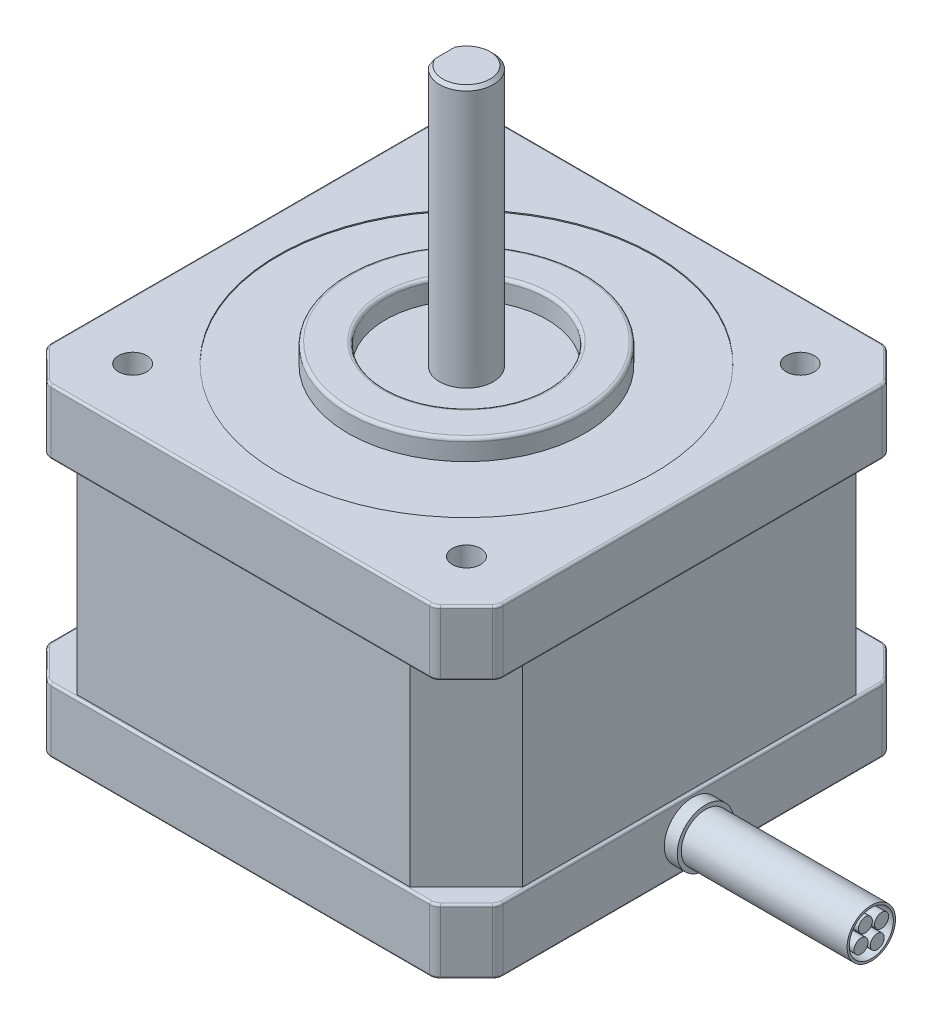
SolidWorks part; units mm, degrees
ref_plane "前视基准面" through (0, 0, 0) normal (0, 0, 1) x (1, 0, 0)
ref_plane "上视基准面" through (0, 0, 0) normal (0, 1, 0) x (1, 0, 0)
ref_plane "右视基准面" through (0, 0, 0) normal (1, 0, 0) x (0, 0, -1)
sketch "草图13" plane through (0, 0, 0) normal (0, 0, 1) x (1, 0, 0)
  line L0 (0, 0) -> (0, 30) construction
  dimension "L" = 30
sketch "草图1" plane through (0, 0, 0) normal (0, 1, 0) x (1, 0, 0)
  line L0 (0, 21) -> (0, -21) construction
  line L1 (-21, 21) -> (21, 21)
  line L2 (-21, 21) -> (-21, -21)
  line L3 (-21, -21) -> (21, -21)
  line L4 (21, 21) -> (21, -21)
  line L5 (-21, 0) -> (21, 0) construction
  dimension "D2" = 21
  dimension "W2" = 42
  dimension "D4" = 21
extrude "凸台-拉伸1" add sketch "草图1" along normal blind 30
chamfer "倒角3" distance 3 angle 45 4 edges at (21, 15, -21) (21, 15, 21) (-21, 15, 21) (-21, 15, -21)
sketch "草图2" plane through (0, 30, 0) normal (0, 1, 0) x (1, 0, 0)
  circle A0 centre (0, 0) radius 11
  dimension "E6" = 22
extrude "凸台-拉伸2" add sketch "草图2" along normal blind 1.8
ref_plane "基准面1" through (0, 6, 0) normal (0, -1, 0) x (1, 0, 0)
sketch "草图3" plane through (0, 30, 0) normal (0, 1, 0) x (1, 0, 0)
  line L0 (-2, 1.5) -> (-2, -1.5) construction
  circle A0 centre (0, 0) radius 2.5
  point P3 (2.5, 0)
  dimension "D1" = 4.5
  dimension "E4" = 5
extrude "凸台-拉伸3" add sketch "草图3" along normal blind 24
sketch "草图4" plane through (0, 6, 0) normal (0, -1, 0) x (1, 0, 0)
  line L0 (15.4716, 20.7) -> (-15.4716, 20.7)
  line L1 (-15.4716, 20.7) -> (-20.7, 15.4716)
  line L2 (-20.7, 15.4716) -> (-20.7, -15.4716)
  line L3 (-20.7, -15.4716) -> (-15.4716, -20.7)
  line L4 (-15.4716, -20.7) -> (15.4716, -20.7)
  line L5 (15.4716, -20.7) -> (20.7, -15.4716)
  line L6 (20.7, -15.4716) -> (20.7, 15.4716)
  line L7 (20.7, 15.4716) -> (15.4716, 20.7)
  line L8 (18, -21) -> (-18, -21) construction
  line L9 (-21, -18) -> (-21, 18) construction
  line L10 (21, 18) -> (21, -18) construction
  line L11 (-18, 21) -> (18, 21) construction
  line L15 (-18, 21) -> (-21, 18) construction
  line L21 (0, -21) -> (0, 21) construction
  line L22 (0, -21) -> (0, 21) construction
  line L23 (-21, 0) -> (21, 0) construction
  dimension "D1" = 0.3
  dimension "D2" = 0.3
  dimension "D3" = 0.3
  dimension "D4" = 0.3
  dimension "D5" = 2
extrude "切除-拉伸1" cut sketch "草图4" against normal blind 18 flip side to cut
fillet "圆角2" radius 1 16 edges at (21, 3, 18) (18, 3, 21) (-18, 3, 21) (-21, 3, 18) (21, 3, -18) (18, 3, -21) (-18, 3, -21) (-21, 3, -18) (-18, 27, -21) (-21, 27, -18) (21, 27, -18) (18, 27, -21) (21, 27, 18) (18, 27, 21) (-18, 27, 21) (-21, 27, 18)
fillet "圆角3" radius 0.2 64 edges at (-21, 24, 0) (-20.9239, 24, 17.9685) (0, 24, 21) (-17.9685, 24, 20.9239) (0, 6, 21) (17.9685, 6, 20.9239) (21, 6, 0) (20.9239, 6, 17.9685) (17.9685, 24, 20.9239) (21, 24, 0) (20.9239, 24, 17.9685) (-21, 6, 0) (-20.9239, 6, 17.9685) (-17.9685, 6, 20.9239) (0, 6, -21) (-17.9685, 6, -20.9239) (-20.9239, 6, -17.9685) (0, 24, -21) (-17.9685, 24, -20.9239) (-20.9239, 24, -17.9685) (-20.9239, 30, -17.9685) (-19.5, 30, -19.5) (-17.9685, 30, -20.9239) (0, 30, -21) (17.9685, 30, -20.9239) (19.5, 30, -19.5) (20.9239, 30, -17.9685) (21, 30, 0) (20.9239, 30, 17.9685) (19.5, 30, 19.5) (17.9685, 30, 20.9239) (0, 30, 21) (-17.9685, 30, 20.9239) (-20.9239, 30, 17.9685) (-20.9239, 0, -17.9685) (-21, 0, 0) (-20.9239, 0, 17.9685) (-19.5, 0, 19.5) (-17.9685, 0, 20.9239) (0, 0, 21) (17.9685, 0, 20.9239) (19.5, 0, 19.5) (20.9239, 0, 17.9685) (21, 0, 0) (20.9239, 0, -17.9685) (19.5, 0, -19.5) (17.9685, 0, -20.9239) (0, 0, -21) (-17.9685, 0, -20.9239) (-19.5, 30, 19.5) (-19.5, 24, 19.5) (19.5, 6, 19.5) (19.5, 24, 19.5) (-19.5, 6, 19.5) (-19.5, 6, -19.5) (-19.5, 24, -19.5) (-21, 30, 0) (-19.5, 0, -19.5) (17.9685, 6, -20.9239) (19.5, 6, -19.5) (20.9239, 6, -17.9685) (17.9685, 24, -20.9239) (19.5, 24, -19.5) (20.9239, 24, -17.9685)
sketch "草图14" plane through (0, 54, 0) normal (0, 1, 0) x (1, 0, 0)
  line L0 (-2, 1.5) -> (-2, -1.5) construction
  line L1 (-2, 1.5) -> (-2, -1.5)
  circle A1 centre (0, 0) radius 2.5 construction
  arc A2 (-2, 1.5) -> (-2, -1.5) centre (0, 0) ccw
extrude "切除-拉伸5" cut sketch "草图14" against normal blind 15
chamfer "倒角5" distance 0.3 angle 45 1 edges at (2.5, 54, 0)
chamfer "倒角4" distance 0.5 angle 45 1 edges at (-2, 39, 0)
chamfer "倒角6" [suppressed] distance 1 angle 45
sketch "草图6" plane through (0, 30, 0) normal (0, 1, 0) x (1, 0, 0)
  line L0 (0, 21) -> (0, -21) construction
  line L3 (-21, 0) -> (21, 0) construction
  line L7 (-21, -21) -> (21, -21) construction
  circle A0 centre (-15.5, 15.5) radius 1.3105
  circle A1 centre (15.5, 15.5) radius 1.3105
  circle A2 centre (15.5, -15.5) radius 1.3105
  circle A3 centre (-15.5, -15.5) radius 1.3105
  dimension "D1" = 31
  dimension "E2" = 2.621
  dimension "E1" = 15.5
extrude "切除-拉伸2" cut sketch "草图6" against normal blind 4.5
cosmetic thread "装饰螺纹线1" parameters "D2"=3
cosmetic thread "装饰螺纹线2" parameters "D2"=3
cosmetic thread "装饰螺纹线3" parameters "D2"=3
cosmetic thread "装饰螺纹线4" parameters "D2"=3
sketch "草图7" plane through (0, 31.8, 0) normal (0, 1, 0) x (1, 0, 0)
  circle A0 centre (0, 0) radius 7.5
  circle A1 centre (0, 0) radius 2.5
  dimension "D1" = 15
  dimension "D2" = 5
extrude "切除-拉伸3" cut sketch "草图7" against normal blind 2
sketch "草图8" plane through (21, 0, 0) normal (1, 0, 0) x (0, 0, -1)
  line L0 (0, 6) -> (0, 0) construction
  line L2 (-15.1716, 6) -> (-18, 6) construction
  circle A0 centre (0, 3) radius 2.625
  dimension "D1" = 5.25
extrude "凸台-拉伸5" add sketch "草图8" along normal blind 1.2
sketch "草图9" plane through (22.2, 0, 0) normal (1, 0, 0) x (0, 0, -1)
  circle A0 centre (0, 3) radius 2.25
  circle A1 centre (0, 3) radius 2.05
  circle A2 centre (0, 3) radius 2.625 construction
  dimension "D1" = 4.5
  dimension "D2" = 0.2
extrude "凸台-拉伸6" add sketch "草图9" along normal blind 15.4
sketch "草图10" plane through (22.2, 0, 0) normal (1, 0, 0) x (0, 0, -1)
  line L0 (0, 3) -> (-0.9526, 3.55) construction
  line L1 (0, 3) -> (0.9526, 3.55) construction
  line L2 (0, 3) -> (0, 1.9) construction
  circle A0 centre (-0.9526, 3.55) radius 0.65 construction
  circle A1 centre (0.9526, 3.55) radius 0.65
  circle A2 centre (0, 1.9) radius 0.65 construction
  circle A5 centre (0, 3) radius 1.1 construction
  dimension "D1" = 120
  dimension "D2" = 2.2
  dimension "D3" = 1.3
  dimension "D4" = 120
extrude "凸台-拉伸8" add sketch "草图10" along normal blind 15.4 contours A0 | A2 | A1
sketch "草图15" plane through (0, 30, 0) normal (0, 1, 0) x (1, 0, 0)
  circle A0 centre (0, 0) radius 17.5
  circle A1 centre (0, 0) radius 11 construction
  circle A2 centre (0, 0) radius 11
  dimension "D1" = 35
extrude "切除-拉伸6" cut sketch "草图15" against normal blind 0.1
fillet "圆角4" radius 0.3 2 edges at (0, 31.8, 7.5) (0, 31.8, 11)
pattern_circular "阵列(圆周)3" count 4 over 360 about axis through (0, 3, 0) along (1, 0, 0) of "凸台-拉伸8"
sketch "草图16" [suppressed] plane through (0, 0, -20.85) normal (0, 0, -1) x (-1, 0, 0)
  line L0 (0, 36.8) -> (0, 9.2) construction
  line L1 (15.6216, 36.8) -> (-15.6216, 36.8) construction
  line L2 (15.6216, 9.2) -> (-15.6216, 9.2) construction
  line L4 (-12.5, 7.2) -> (12.5, 7.2)
  line L5 (-12.5, 7.2) -> (-12.5, 38.8)
  line L6 (-12.5, 38.8) -> (12.5, 38.8)
  line L7 (12.5, 7.2) -> (12.5, 38.8)
  line L8 (-12.5, 7.2) -> (12.5, 38.8) construction
  line L9 (-12.5, 38.8) -> (12.5, 7.2) construction
  point P6 (0, 23)
  dimension "D1" = 2
  dimension "D2" = 25
extrude "切除-拉伸9" [suppressed] cut sketch "草图16" along normal blind 0.3
sketch "草图17" [suppressed] plane through (0, 0, 20.85) normal (0, 0, 1) x (1, 0, 0)
  line L4 (-12.5, 7.2) -> (12.5, 7.2)
  line L5 (-12.5, 38.8) -> (-12.5, 7.2)
  line L6 (12.5, 38.8) -> (-12.5, 38.8)
  line L7 (12.5, 7.2) -> (12.5, 38.8)
  line L8 (-12.5, 7.2) -> (12.5, 7.2)
  line L9 (-12.5, 38.8) -> (-12.5, 7.2)
  line L10 (12.5, 38.8) -> (-12.5, 38.8)
  line L11 (12.5, 7.2) -> (12.5, 38.8)
  dimension "D1" = 0
extrude "切除-拉伸10" [suppressed] cut sketch "草图17" along normal up to surface (0.3 mm away)
sketch "草图18" [suppressed] plane through (20.85, 0, 0) normal (1, 0, 0) x (0, 0, -1)
  line L0 (0, 9.2) -> (0, 36.8) construction
  line L1 (15.6216, 9.2) -> (-15.6216, 9.2) construction
  line L2 (15.6216, 36.8) -> (-15.6216, 36.8) construction
  line L4 (-12.5, 8.2) -> (12.5, 8.2)
  line L5 (-12.5, 8.2) -> (-12.5, 37.8)
  line L6 (-12.5, 37.8) -> (12.5, 37.8)
  line L7 (12.5, 8.2) -> (12.5, 37.8)
  line L8 (-12.5, 8.2) -> (12.5, 37.8) construction
  line L9 (-12.5, 37.8) -> (12.5, 8.2) construction
  point P6 (0, 23)
  dimension "D1" = 1
  dimension "D2" = 25
extrude "切除-拉伸11" [suppressed] cut sketch "草图18" along normal up to surface (0.3 mm away)
sketch "草图19" [suppressed] plane through (-20.85, 0, 0) normal (-1, 0, 0) x (0, 0, 1)
  line L4 (-12.5, 8.2) -> (12.5, 8.2)
  line L5 (-12.5, 37.8) -> (-12.5, 8.2)
  line L6 (12.5, 37.8) -> (-12.5, 37.8)
  line L7 (12.5, 8.2) -> (12.5, 37.8)
  line L8 (-12.5, 8.2) -> (12.5, 8.2)
  line L9 (-12.5, 37.8) -> (-12.5, 8.2)
  line L10 (12.5, 37.8) -> (-12.5, 37.8)
  line L11 (12.5, 8.2) -> (12.5, 37.8)
  dimension "D1" = 0
extrude "切除-拉伸12" [suppressed] cut sketch "草图19" along normal up to surface (0.3 mm away)
